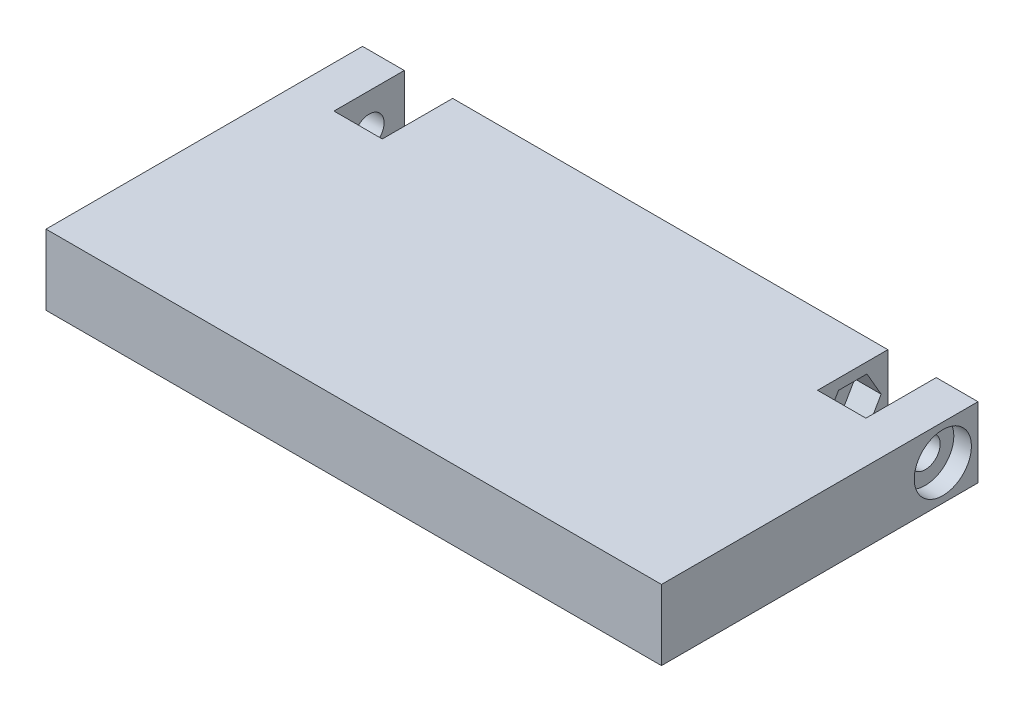
SolidWorks part; units mm, degrees
ref_plane "Front Plane" through (0, 0, 0) normal (0, 0, 1) x (1, 0, 0)
ref_plane "Top Plane" through (0, 0, 0) normal (0, 1, 0) x (1, 0, 0)
ref_plane "Right Plane" through (0, 0, 0) normal (1, 0, 0) x (0, 0, -1)
sketch "Sketch1" plane through (0, 0, 0) normal (0, 1, 0) x (1, 0, 0)
  line L1 (-35, -18) -> (35, -18)
  line L2 (-35, -18) -> (-35, 18)
  line L3 (-35, 18) -> (35, 18)
  line L4 (35, -18) -> (35, 18)
  line L5 (-35, -18) -> (35, 18) construction
  line L6 (-35, 18) -> (35, -18) construction
  point P0 (0, 0)
  dimension "D1" = 70
  dimension "D2" = 36
extrude "Boss-Extrude1" add sketch "Sketch1" along normal blind 8
sketch "Sketch2" plane through (0, 8, 0) normal (0, 1, 0) x (1, 0, 0)
  line L0 (35, 18) -> (-35, 18) construction
  line L1 (-30.25, 18) -> (-24.75, 18)
  line L2 (-30.25, 18) -> (-30.25, 10)
  line L3 (-30.25, 10) -> (-24.75, 10)
  line L4 (-24.75, 18) -> (-24.75, 10)
  line L5 (0, 0) -> (0, 18) construction
  line L6 (24.75, 18) -> (24.75, 10)
  line L7 (30.25, 10) -> (24.75, 10)
  line L8 (30.25, 18) -> (30.25, 10)
  line L9 (30.25, 18) -> (24.75, 18)
  dimension "D1" = 5.5
  dimension "D2" = 8
  dimension "D3" = 49.5
extrude "Cut-Extrude1" cut sketch "Sketch2" against normal through all
hole_wizard "CBORE for M3 Cheese Head Screw1" positions "Sketch7" profile "Sketch8" counterbore size "M3" standard "ISO" end condition up to next
sketch "Sketch7" plane through (35, 0, 0) normal (1, 0, 0) x (0, 0, -1)
  line L0 (-18, 8) -> (18, 8) construction
  line L1 (18, 8) -> (18, 0) construction
  point P0 (14, 4)
  dimension "D1" = 4
  dimension "D2" = 4
sketch "Sketch8" plane through (35, 4, -14) normal (0, 1, 0) x (0, 0, -1)
  line L0 (0, 0) -> (0, 59.75)
  line L1 (0, 59.75) -> (1.7, 59.75)
  line L3 (1.7, 59.75) -> (1.7, 2)
  line L4 (1.7, 2) -> (3.25, 2)
  line L5 (3.25, 2) -> (3.25, 0)
  line L7 (3.25, 0) -> (0, 0)
  line L11 (0, -6.35) -> (0, 107.95) construction
  dimension "Thru Hole Dia." = 3.4
  dimension "Thru Hole Depth" = 59.75
  dimension "C'Bore Dia." = 6.5
  dimension "C'Bore Depth" = 2
sketch "Sketch9" plane through (24.75, 0, 0) normal (1, 0, 0) x (0, 0, -1)
  line L1 (15.6166, 6.8) -> (12.3834, 6.8)
  line L2 (12.3834, 6.8) -> (10.7668, 4)
  line L3 (10.7668, 4) -> (12.3834, 1.2)
  line L4 (12.3834, 1.2) -> (15.6166, 1.2)
  line L5 (15.6166, 1.2) -> (17.2332, 4)
  line L6 (17.2332, 4) -> (15.6166, 6.8)
  circle A0 centre (14, 4) radius 2.8 construction
  dimension "D1" = 5.6
extrude "Cut-Extrude2" cut sketch "Sketch9" against normal blind 3
mirror "Mirror1" about plane through (0, 0, 0) normal (1, 0, 0) of "Cut-Extrude2", "CBORE for M3 Cheese Head Screw1"
